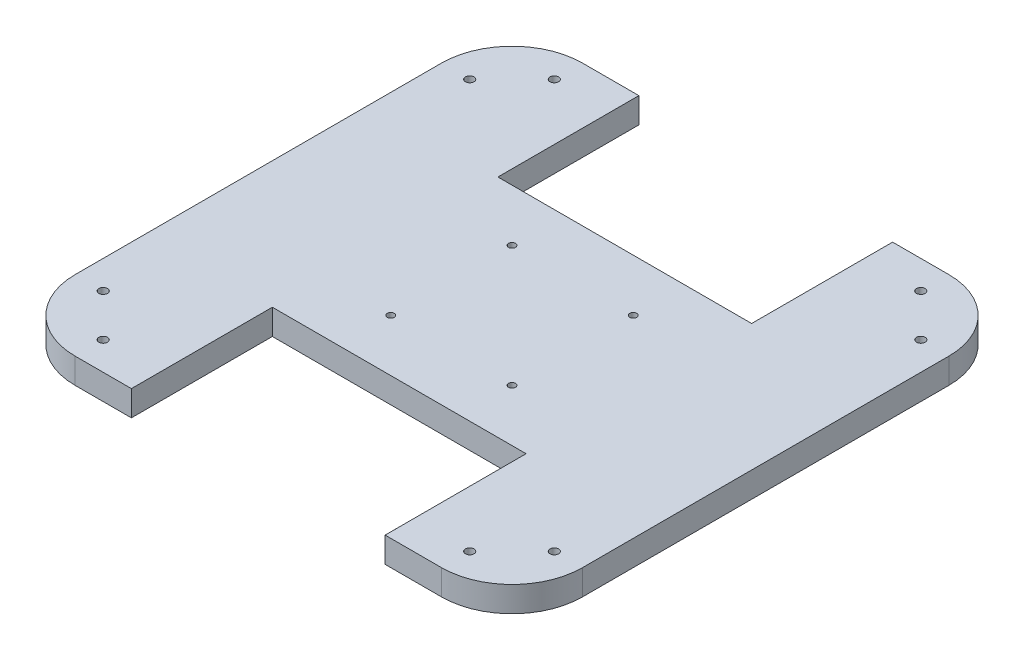
SolidWorks part; units mm, degrees
ref_plane "Front Plane" through (0, 0, 0) normal (0, 0, 1) x (1, 0, 0)
ref_plane "Top Plane" through (0, 0, 0) normal (0, 1, 0) x (1, 0, 0)
ref_plane "Right Plane" through (0, 0, 0) normal (1, 0, 0) x (0, 0, -1)
sketch "Sketch1" plane through (0, 0, 0) normal (0, 1, 0) x (1, 0, 0)
  line L1 (-65, -90) -> (65, -90)
  line L2 (-90, -65) -> (-90, 65)
  line L3 (-65, 90) -> (65, 90)
  line L4 (90, -65) -> (90, 65)
  arc A0 (-90, 65) -> (-65, 90) centre (-65, 65) cw
  arc A1 (65, 90) -> (90, 65) centre (65, 65) cw
  arc A2 (90, -65) -> (65, -90) centre (65, -65) cw
  arc A3 (-65, -90) -> (-90, -65) centre (-65, -65) cw
  point P4 (-90, 0)
  point P6 (0, 90)
  dimension "D3" = 25
  dimension "D1" = 180
  dimension "D2" = 180
extrude "Plate" add sketch "Sketch1" along normal blind 9
sketch "Sketch3" plane through (0, 9, 0) normal (0, 1, 0) x (1, 0, 0)
  line L0 (-65, 90) -> (-65, -90) construction
  line L1 (65, 90) -> (65, -90) construction
  line L2 (-90, 65) -> (90, 65) construction
  line L3 (-90, -65) -> (90, -65) construction
  circle A0 centre (-65, 80) radius 1.525
  circle A1 centre (-80, 65) radius 1.525
  circle A2 centre (80, 65) radius 1.525
  circle A3 centre (80, -65) radius 1.525
  circle A4 centre (65, 80) radius 1.525
  circle A5 centre (65, -80) radius 1.525
  circle A6 centre (-65, -80) radius 1.525
  circle A7 centre (-80, -65) radius 1.525
  dimension "D1" = 3.05
  dimension "D2" = 15
  dimension "D3" = 15
  dimension "D4" = 15
  dimension "D5" = 15
  dimension "D6" = 15
  dimension "D7" = 15
  dimension "D8" = 15
  dimension "D9" = 15
extrude "Hex Holes" cut sketch "Sketch3" against normal through all
sketch "Sketch4" plane through (0, 9, 0) normal (0, 1, 0) x (1, 0, 0)
  line L0 (-90, -65) -> (-90, 65) construction
  line L1 (-65, -90) -> (65, -90) construction
  circle A0 centre (-21.5, 21.5) radius 1.25
  circle A1 centre (21.5, 21.5) radius 1.25
  circle A2 centre (21.5, -21.5) radius 1.25
  circle A3 centre (-21.5, -21.5) radius 1.25
  dimension "D1" = 2.5
  dimension "D2" = 43
  dimension "D3" = 43
  dimension "D4" = 68.5
  dimension "D5" = 68.5
extrude "LiDAR Holes" cut sketch "Sketch4" against normal through all
sketch "Sketch5" plane through (0, 9, 0) normal (0, 1, 0) x (1, 0, 0)
  line L0 (-65, 90) -> (65, 90) construction
  line L1 (45, 90) -> (-45, 90)
  line L2 (45, 90) -> (45, 40)
  line L3 (45, 40) -> (-45, 40)
  line L4 (-45, 90) -> (-45, 40)
  line L5 (-65, -90) -> (65, -90) construction
  line L6 (45, -90) -> (-45, -90)
  line L7 (45, -90) -> (45, -40)
  line L8 (45, -40) -> (-45, -40)
  line L9 (-45, -90) -> (-45, -40)
  point P6 (0, 90)
  point P7 (0, 90)
  point P14 (0, -90)
  point P15 (0, -90)
  dimension "D1" = 90
  dimension "D2" = 50
  dimension "D3" = 50
  dimension "D4" = 90
extrude "Cut-Extrude1" cut sketch "Sketch5" against normal through all
